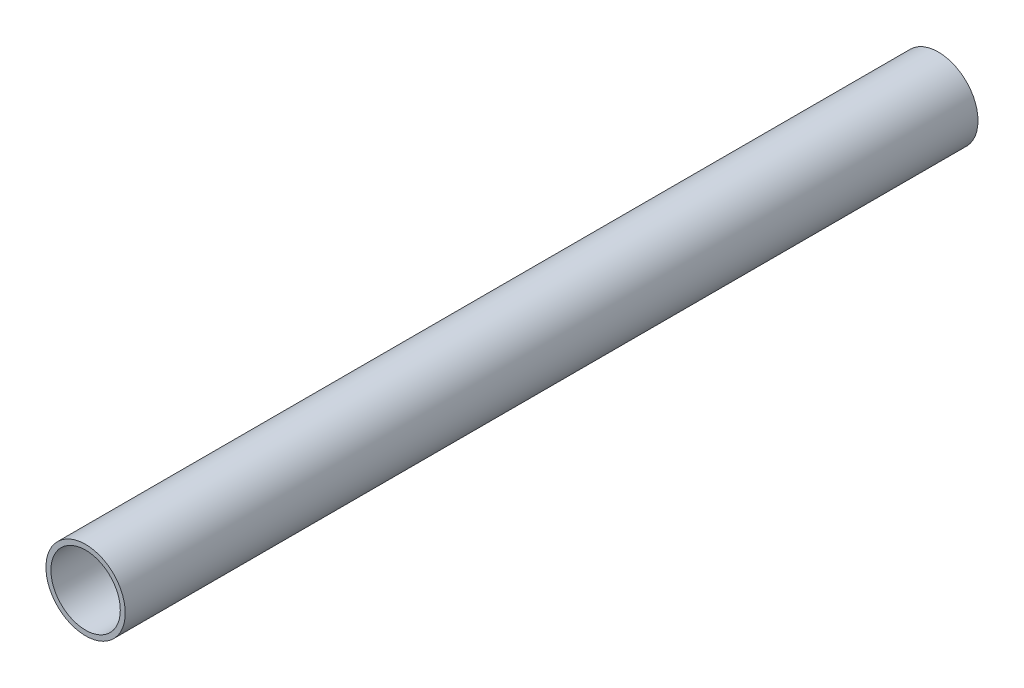
SolidWorks part; units mm, degrees
material "PC High Viscosity"
ref_plane "Front Plane" through (0, 0, 0) normal (0, 0, 1) x (1, 0, 0)
ref_plane "Top Plane" through (0, 0, 0) normal (0, 1, 0) x (1, 0, 0)
ref_plane "Right Plane" through (0, 0, 0) normal (1, 0, 0) x (0, 0, -1)
sketch "Sketch1" plane through (0, 0, 0) normal (0, 0, 1) x (1, 0, 0)
  circle A0 centre (0, 0) radius 22.225
  circle A1 centre (0, 0) radius 25.4
  dimension "D1" = 50.8
  dimension "D2" = 44.45
extrude "Boss-Extrude1" add sketch "Sketch1" along normal mid plane 546.1
